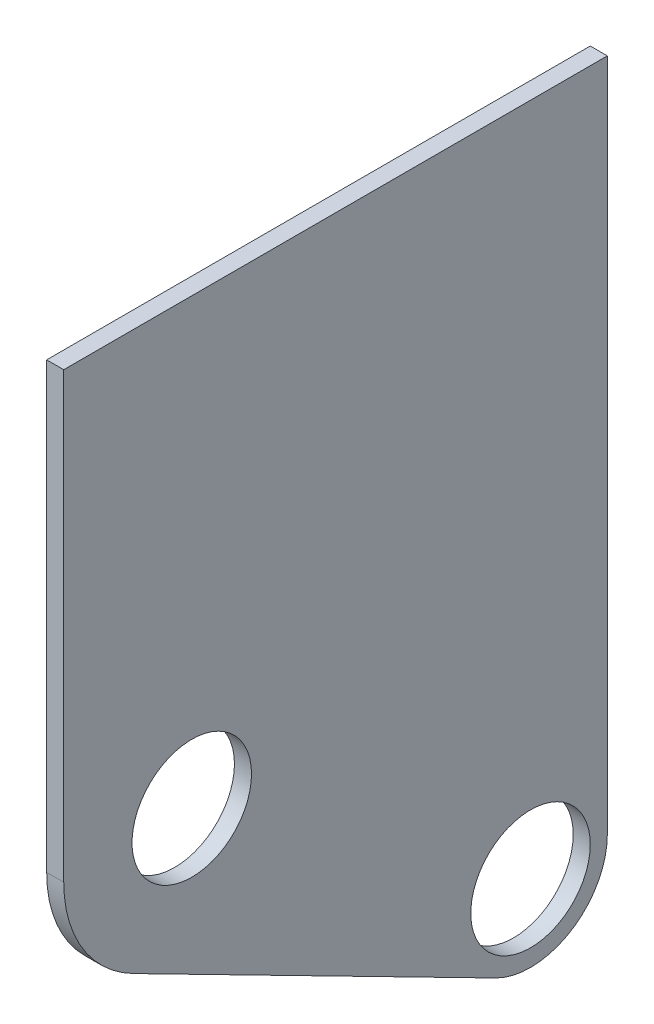
SolidWorks part; units mm, degrees
material "6061-T6 (SS)"
ref_plane "Front" through (0, 0, 0) normal (0, 0, 1) x (1, 0, 0)
ref_plane "Top" through (0, 0, 0) normal (0, 1, 0) x (1, 0, 0)
ref_plane "Right" through (0, 0, 0) normal (1, 0, 0) x (0, 0, -1)
sketch "Sketch2" plane through (0, 0, 0) normal (1, 0, 0) x (0, 0, -1)
  line L0 (50.551, 0) -> (-50.551, 0)
  line L1 (-50.551, 0) -> (-50.551, -82.55)
  line L2 (-37.5669, -103.758) -> (29.7664, -138.1373)
  line L3 (50.551, -125.4125) -> (50.551, 0)
  line L4 (214.7999, -146.05) -> (-214.7999, -146.05) construction
  line L5 (-50.551, -50.8) -> (50.551, -50.8) construction
  circle A0 centre (-26.7385, -82.55) radius 11.1125
  circle A1 centre (36.2635, -125.4125) radius 11.1125
  circle A2 centre (-26.7385, -82.55) radius 25.4 construction
  circle A3 centre (36.2635, -125.4125) radius 12.7 construction
  arc A4 (-50.551, -82.55) -> (-37.5669, -103.758) centre (-26.7385, -82.55) ccw
  arc A5 (29.7664, -138.1373) -> (50.551, -125.4125) centre (36.2635, -125.4125) ccw
  point P4 (0, 0)
  point P17 (0, -146.05)
  dimension "D1" = 22.225
  dimension "D2" = 50.8
  dimension "D3" = 25.4
  dimension "D4" = 38.1
  dimension "D5" = 3.175
  dimension "D6" = 12.7
  dimension "D7" = 6.35
  dimension "D8" = 38.1
  dimension "D9" = 50.8
  dimension "D10" = 95.25
extrude "Boss-Extrude1" add sketch "Sketch2" along normal blind 3.175
